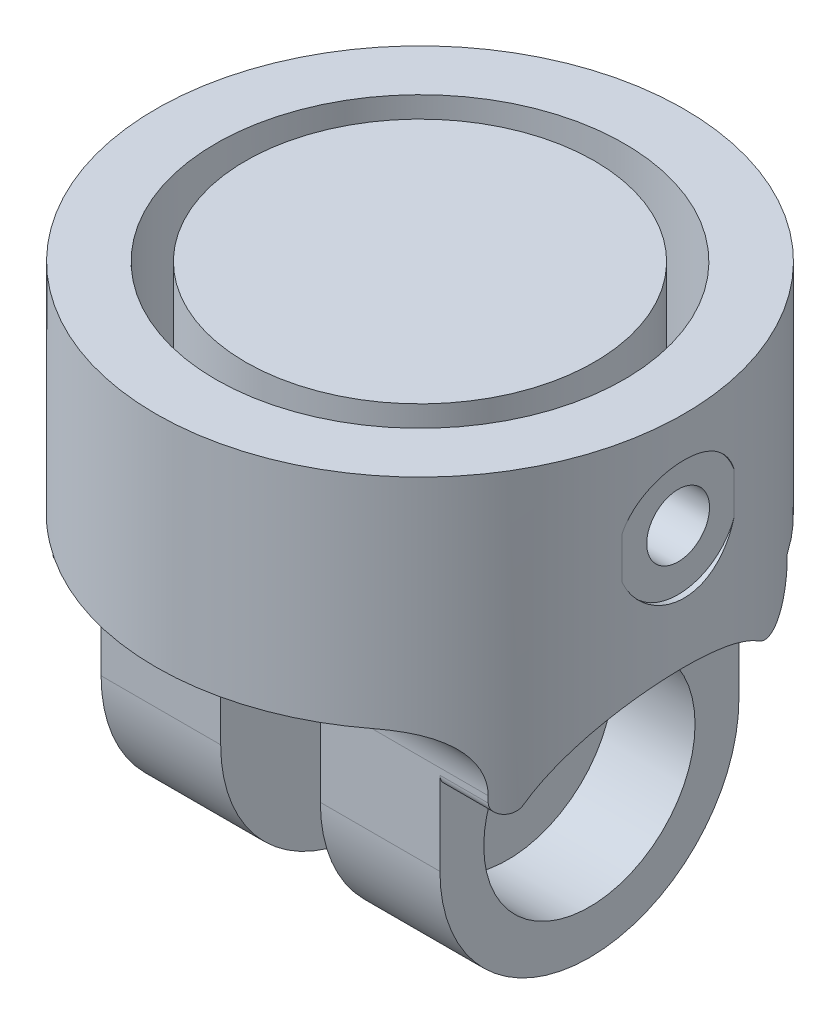
SolidWorks part; units mm, degrees
material "PLA Black"
ref_plane "Front" through (0, 0, 0) normal (0, 0, 1) x (1, 0, 0)
ref_plane "Top" through (0, 0, 0) normal (0, 1, 0) x (1, 0, 0)
ref_plane "Right" through (0, 0, 0) normal (1, 0, 0) x (0, 0, -1)
sketch "Sketch1" plane through (0, 0, 0) normal (0, 1, 0) x (1, 0, 0)
  line L0 (0, 8.75) -> (0, 10.25) construction
  circle A0 centre (0, 0) radius 10.25
  circle A1 centre (0, 0) radius 13.25
  circle A2 centre (0, 0) radius 9.5 construction
  circle A4 centre (0, 0) radius 8.75
  point P11 (0, 9.5)
  dimension "D1" = 1.5
  dimension "D2" = 3
  dimension "D3" = 19
extrude "Boss-Extrude1" add sketch "Sketch1" along normal blind 10 contours A1 A0 | A4 region at (-12.8752, 0, 0) region at (0, 0, 0)
sketch "Sketch3" plane through (0, 0, 0) normal (0, -1, 0) x (1, 0, 0)
  circle A2 centre (0, 0) radius 13.25 construction
  circle A3 centre (0, 0) radius 13.25
extrude "Boss-Extrude2" add sketch "Sketch3" along normal blind 1
sketch "Sketch4" plane through (0, -1, 0) normal (0, -1, 0) x (1, 0, 0)
  line L0 (0, 17.8908) -> (0, -17.0763) construction
  line L1 (2.5, 7.5) -> (8.5, 7.5)
  line L2 (2.5, 7.5) -> (2.5, -7.5)
  line L3 (2.5, -7.5) -> (8.5, -7.5)
  line L4 (8.5, 7.5) -> (8.5, -7.5)
  line L5 (-8.5, 7.5) -> (-8.5, -7.5)
  line L6 (-2.5, -7.5) -> (-8.5, -7.5)
  line L7 (-2.5, 7.5) -> (-2.5, -7.5)
  line L8 (-2.5, 7.5) -> (-8.5, 7.5)
  line L9 (16.8049, 0) -> (-19.8998, 0) construction
  dimension "D1" = 6
  dimension "D2" = 5
  dimension "D3" = 15
extrude "Boss-Extrude3" add sketch "Sketch4" along normal blind 15
sketch "Sketch5" plane through (8.5, 0, 0) normal (1, 0, 0) x (0, 0, -1)
  line L0 (-7.5, -16) -> (-7.5, -1) construction
  line L1 (7.5, -16) -> (7.5, -1) construction
  line L2 (7.5, -8.5) -> (7.5, -17.1619)
  line L3 (7.5, -17.1619) -> (-7.5, -17.1619)
  line L4 (-7.5, -17.1619) -> (-7.5, -8.5)
  arc A0 (-7.5, -8.5) -> (7.5, -8.5) centre (0, -8.5) ccw
  circle A1 centre (0, -8.5) radius 1.75
  dimension "D1" = 3.5
extrude "Cut-Extrude1" cut sketch "Sketch5" against normal through all both and the other way through all
sketch "Sketch6" plane through (8.5, 0, 0) normal (1, 0, 0) x (0, 0, -1)
  circle A0 centre (0, -8.5) radius 5.3
  dimension "D1" = 10.6
extrude "Cut-Extrude2" cut sketch "Sketch6" against normal blind 4.1
mirror "Mirror1" about plane through (0, 0, 0) normal (1, 0, 0) of "Cut-Extrude2"
ref_plane "Plane9" through (1.65, 0, 0) normal (1, 0, 0) x (0, 0, -1)
sketch "Sketch7" plane through (1.65, 0, 0) normal (1, 0, 0) x (0, 0, -1)
  line L0 (3.4, -8.5) -> (3.4, -1) construction
  line L1 (7.5, -1) -> (-7.5, -1) construction
  line L2 (3.3065, -7.7081) -> (1.7, -1) construction
  line L3 (3.0306, -6.9587) -> (0, -1) construction
  line L4 (1.7, -0.6757) -> (1.7, -1.4422) construction
  line L5 (2.6419, -6.3598) -> (-1.7, -1) construction
  line L6 (2.2408, -5.9429) -> (-3.4, -1) construction
  line L8 (0, -1.6788) -> (0, 0) construction
  line L9 (-8.4824, -8.5) -> (8.712, -8.5) construction
  line L10 (1.8898, -5.6736) -> (-5.1, -1) construction
  line L11 (-3.4, -0.3587) -> (-3.4, -1.6788) construction
  circle A0 centre (0, -8.5) radius 3.4 construction
  dimension "D1" = 6.8
  dimension "D2" = 33.768
  dimension "D3" = 7.5
ref_plane "Plane1" through (1.65, -1, -3.4) normal (0, 1, 0) x (1, 0, 0)
ref_plane "Plane2" through (1.65, -1, -1.7) normal (0, 0.9725, 0.2329) x (1, 0, 0)
ref_plane "Plane3" through (1.65, -1, 0) normal (0, 0.8913, 0.4533) x (1, 0, 0)
ref_plane "Plane5" through (1.65, -1, 1.7) normal (0, 0.777, 0.6295) x (1, 0, 0)
ref_plane "Plane6" through (1.65, -1, 3.4) normal (0, 0.659, 0.7521) x (1, 0, 0)
ref_plane "Plane7" through (1.65, -1, 5.1) normal (0, 0.5558, 0.8313) x (1, 0, 0)
sketch "Sketch8" plane through (1.65, -1, -3.4) normal (0, 1, 0) x (1, 0, 0)
  circle A0 centre (0, 0) radius 0.605
  dimension "D1" = 1.21
extrude "Cut-Extrude5" cut sketch "Sketch8" along normal blind 5.5 and the other way through all
sketch "Sketch9" plane through (1.65, -1, -1.7) normal (0, 0.9725, 0.2329) x (1, 0, 0)
  circle A0 centre (0, 0) radius 0.605
  dimension "D1" = 1.21
extrude "Cut-Extrude3" cut sketch "Sketch9" along normal blind 5.5
sketch "Sketch10" plane through (1.65, -1, 0) normal (0, 0.8913, 0.4533) x (1, 0, 0)
  circle A0 centre (0, 0) radius 0.605
  dimension "D1" = 1.21
sketch "Sketch11" plane through (1.65, -1, 1.7) normal (0, 0.777, 0.6295) x (1, 0, 0)
  circle A0 centre (0, 0) radius 0.605
  dimension "D1" = 1.21
sketch "Sketch12" plane through (1.65, -1, 3.4) normal (0, 0.659, 0.7521) x (1, 0, 0)
  circle A0 centre (0, 0) radius 0.605
  dimension "D1" = 1.21
sketch "Sketch14" plane through (1.65, -1, 5.1) normal (0, 0.5558, 0.8313) x (1, 0, 0)
  circle A0 centre (0, 0) radius 0.605
  dimension "D1" = 1.21
extrude "Cut-Extrude6" cut sketch "Sketch10" along normal blind 5.5 and the other way through all
extrude "Cut-Extrude7" cut sketch "Sketch11" along normal blind 5.5 and the other way through all contours A0
extrude "Cut-Extrude8" cut sketch "Sketch12" along normal blind 5.5 and the other way through all contours A0
extrude "Cut-Extrude9" cut sketch "Sketch14" along normal blind 5.5 and the other way through all contours A0
ref_plane "Plane8" through (13.25, 0, 0) normal (1, 0, 0) x (0, 0, -1)
hole_wizard "Tap Drill for M3 Helicoil1" positions "Sketch17" profile "Sketch18" hole size "M3x0.5" standard "DIN"
sketch "Sketch17" plane through (13.25, 0, 0) normal (1, 0, 0) x (0, 0, -1)
  line L0 (-22.2973, 5) -> (18.0703, 5) construction
  line L4 (0, 12.2732) -> (0, -5.3405) construction
  line L6 (-7.5, -8.5) -> (-7.5, -1) construction
  line L7 (7.5, -8.5) -> (7.5, -1) construction
  line L8 (13.25, 10) -> (-13.25, 10) construction
  line L9 (10.25, 0) -> (-10.25, 0) construction
  point P0 (0, 5)
sketch "Sketch18" plane through (13.25, 5, 0) normal (0, 1, 0) x (0, 0, -1)
  line L0 (0, 0) -> (0, 6.9464)
  line L1 (0, 6.9464) -> (1.575, 6)
  line L2 (1.575, 6) -> (1.575, 0)
  line L5 (1.575, 0) -> (0, 0)
  line L10 (0, 6.9464) -> (-1.575, 6) construction
  line L11 (0, -6.35) -> (0, 107.95) construction
  dimension "Hole Dia." = 3.15
  dimension "Hole Depth" = 6
  dimension "Drill Angle" = 118
sketch "Sketch20" plane through (13.25, 0, 0) normal (1, 0, 0) x (0, 0, -1)
  circle A0 centre (0, 5) radius 3
  dimension "D1" = 6
extrude "Cut-Extrude10" cut sketch "Sketch20" against normal blind 0.3
sketch "Sketch21" plane through (8.5, 0, 0) normal (1, 0, 0) x (0, 0, -1)
  line L0 (7.5, -1) -> (-7.5, -1) construction
  line L1 (7.5, -0.1252) -> (7.5, -1.1767)
  line L2 (0.9244, -19.0662) -> (-4.8209, -14.2453) construction
  line L3 (0, 5.2718) -> (0, -9.2894) construction
  line L4 (0, 10) -> (0, -1) construction
  line L5 (-7.5, -0.1252) -> (-7.5, -4.3226)
  line L6 (7.5, -0.1252) -> (-7.5, -0.1252)
  line L7 (-7.5, -8.5) -> (-7.5, -1) construction
  line L8 (7.5, -8.5) -> (7.5, -1) construction
  line L9 (0, -1) -> (9.4693, -4.4465) construction
  line L10 (0, -1) -> (1.6171, -0.0664) construction
  line L11 (4.6128, -2.5863) -> (7.5, -1.1767) construction
  line L12 (10.5662, -7.5756) -> (4.8209, -2.7547) construction
  line L13 (-4.8209, -14.2453) -> (4.8209, -2.7547) construction
  line L14 (10.5662, -7.5756) -> (0.9244, -19.0662) construction
  arc A0 (-6.4204, -4.6233) -> (4.6128, -2.5863) centre (0, -8.5) cw
  arc A1 (-6.4204, -4.6233) -> (-7.5, -4.3226) centre (-6.9183, -4.3226) cw
  arc A2 (7.5, -1.1767) -> (4.6128, -2.5863) centre (5.7123, -1.1767) cw
  circle A3 centre (0, -8.5) radius 1.75 construction
  arc A4 (-4.8209, -14.2453) -> (4.8209, -2.7547) centre (0, -8.5) cw construction
  dimension "D1" = 30
  dimension "D3" = 7.5
  dimension "D2" = 50
  dimension "D4" = 15
extrude "Boss-Extrude4" add sketch "Sketch21" along normal up to surface (2.423 mm away) up to face at (13.0965, 5, 0)
mirror "Mirror2" about plane through (0, 0, 0) normal (1, 0, 0) of "Boss-Extrude4", "Tap Drill for M3 Helicoil1", "Cut-Extrude10"
fillet "Fillet1" radius 3 2 edges at (-6.7115, -1, 7.5) (6.7115, -1, 7.5)
equation "\"knee_angle\"= 70"
equation "\"ankle_angle\" = 80"
equation "\"hip_angle\" = 40"
equation "\"spring_ankle_parallel_arm_diameter\"= 1.1"
equation "\"spring_ankle_parallel_arm_length\"= 13"
equation "\"spring_ankle_parallel_intern_diameter\"= 5.7"
equation "\"spring_ankle_parallel_angle\"= \"ankle_angle\""
equation "\"spring_ankle_parallel_turns\"= 3"
equation "\"spring_ankle_parallel_pitch\"= \"spring_ankle_parallel_arm_diameter\" * 1.01"
equation "\"spring_ankle_parallel_cutting_distance\"= (1-\"spring_ankle_parallel_angle\" / 360) * \"spring_ankle_parallel_pitch\""
equation "\"spring_ankle_serial_arm_diameter\"= 1.91"
equation "\"spring_ankle_serial_arm_length\"= 10"
equation "\"spring_ankle_serial_intern_diameter\"= 5.7"
equation "\"spring_ankle_serial_angle\"= \"90\""
equation "\"spring_ankle_serial_turns\"= 3"
equation "\"spring_ankle_serial_pitch\"= \"spring_ankle_serial_arm_diameter\" * 1.01"
equation "\"spring_ankle_serial_cutting_distance\"= (1-\"spring_ankle_serial_angle\" / 360) * \"spring_ankle_serial_pitch\""
equation "\"spring_knee_parallel_arm_diameter\"= 1.1"
equation "\"spring_knee_parallel_arm_length\"= 13"
equation "\"spring_knee_parallel_intern_diameter\"= 5.7"
equation "\"spring_knee_parallel_angle\"= -\"knee_angle\" + 90"
equation "\"spring_knee_parallel_turns\"= 3"
equation "\"spring_knee_parallel_pitch\"= \"spring_knee_parallel_arm_diameter\" * 1.01"
equation "\"spring_knee_parallel_cutting_distance\"= (1-(\"spring_knee_parallel_angle\") / 360) * \"spring_knee_parallel_pitch\""
equation "\"spring_knee_serial_arm_diameter\"= 1.91"
equation "\"spring_knee_serial_arm_length\"= 10"
equation "\"spring_knee_serial_intern_diameter\"= 5.7"
equation "\"spring_knee_serial_angle\"= \"90\""
equation "\"spring_knee_serial_turns\"= 3"
equation "\"spring_knee_serial_pitch\"= \"spring_knee_serial_arm_diameter\" * 1.01"
equation "\"spring_knee_serial_cutting_distance\"= (1-\"spring_knee_serial_angle\" / 360) * \"spring_knee_serial_pitch\""
equation "\"spring_ankle_parallel_nominal_diameter\"= \"spring_ankle_parallel_arm_diameter\" + \"spring_ankle_parallel_intern_diameter\""
equation "\"spring_ankle_serial_nominal_diameter\"= \"spring_ankle_serial_arm_diameter\" + \"spring_ankle_serial_intern_diameter\""
equation "\"spring_knee_parallel_nominal_diameter\"= \"spring_knee_parallel_arm_diameter\" + \"spring_knee_parallel_intern_diameter\""
equation "\"spring_knee_serial_nominal_diameter\"= \"spring_knee_serial_arm_diameter\" + \"spring_knee_serial_intern_diameter\""
equation "\"D1@Sketch7\"=\"spring_ankle_parallel_nominal_diameter\""
equation "\"D1@Sketch8\"=\"spring_ankle_parallel_arm_diameter\"*1.1"
equation "\"D1@Sketch9\"=\"spring_ankle_parallel_arm_diameter\"*1.1"
equation "\"D1@Sketch10\"=\"spring_ankle_parallel_arm_diameter\"*1.1"
equation "\"D1@Sketch11\"=\"spring_ankle_parallel_arm_diameter\"*1.1"
equation "\"D1@Sketch12\"=\"spring_ankle_parallel_arm_diameter\"*1.1"
equation "\"D1@Sketch14\"=\"spring_ankle_parallel_arm_diameter\"*1.1"
equation "\"D1@Cut-Extrude3\"=\"spring_ankle_parallel_arm_length\"-\"axis_structure_distance\""
equation "\"axis_structure_distance\"= 7.5"
equation "\"D1@Cut-Extrude5\"=\"spring_ankle_parallel_arm_length\"-\"axis_structure_distance\""
equation "\"D1@Cut-Extrude6\"=\"spring_ankle_parallel_arm_length\"-\"axis_structure_distance\""
equation "\"D1@Cut-Extrude7\"=\"spring_ankle_parallel_arm_length\"-\"axis_structure_distance\""
equation "\"D1@Cut-Extrude8\"=\"spring_ankle_parallel_arm_length\"-\"axis_structure_distance\""
equation "\"D1@Cut-Extrude9\"=\"spring_ankle_parallel_arm_length\"-\"axis_structure_distance\""
equation "\"D1@Boss-Extrude3\"=\"axis_structure_distance\"*2"
equation "\"ankle_angle_max\" = 120"
equation "\"ankle_angle_min\" = 50"
equation "\"knee_angle_max\" = 120"
equation "\"knee_angle_min\" = 0"
equation "\"hip_angle_max\" = 90"
equation "\"hip_angle_min\" = -60"
equation "\"D1@Sketch21\"=\"ankle_angle_max\"-90"
equation "\"D2@Sketch21\"=\"ankle_angle_min\""
equation "\"D1@Plane9\"=(\"spring_ankle_parallel_arm_diameter\"*\"spring_ankle_parallel_turns\")/2"
